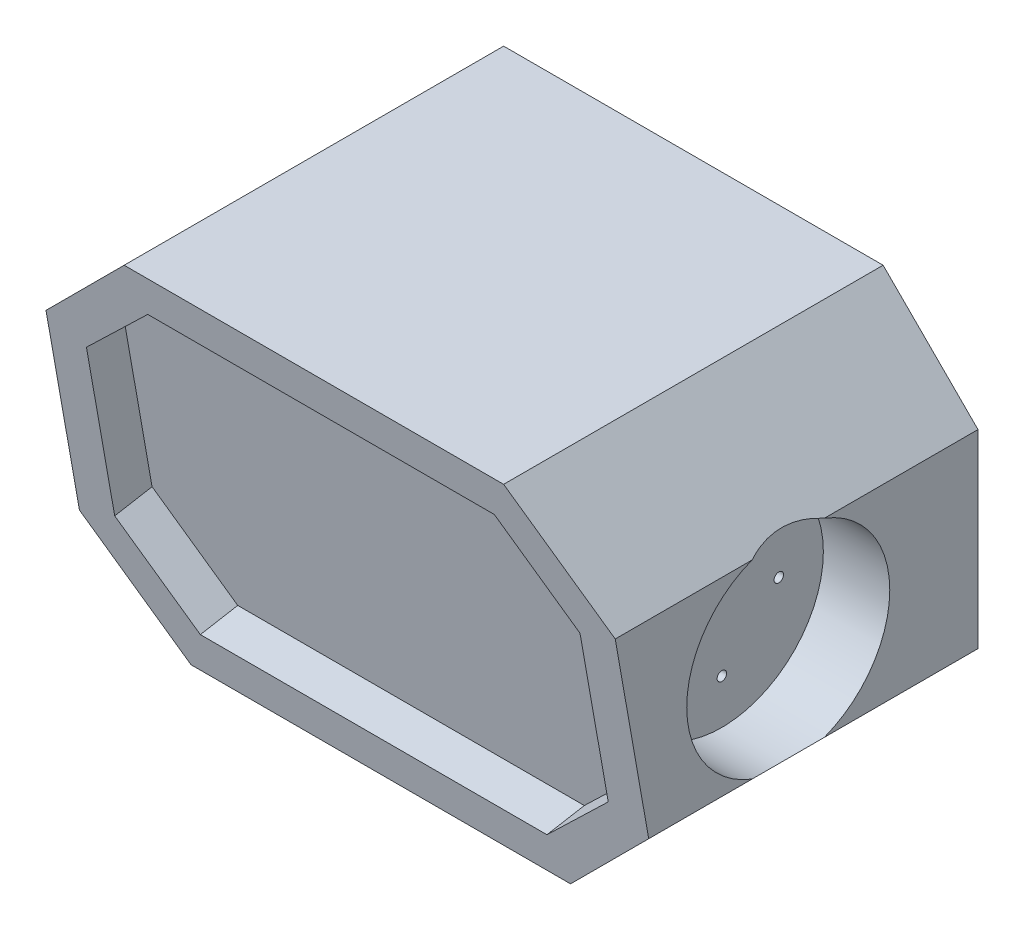
SolidWorks part; units mm, degrees
ref_plane "Front Plane" through (0, 0, 0) normal (0, 0, 1) x (1, 0, 0)
ref_plane "Top Plane" through (0, 0, 0) normal (0, 1, 0) x (1, 0, 0)
ref_plane "Right Plane" through (0, 0, 0) normal (1, 0, 0) x (0, 0, -1)
sketch "Sketch1" plane through (0, 0, 0) normal (1, 0, 0) x (0, 0, -1)
  line L1 (-100, -100) -> (100, -100)
  line L2 (-100, -100) -> (-100, 100)
  line L3 (-100, 100) -> (100, 100)
  line L4 (100, -100) -> (100, 100)
  line L5 (-100, -100) -> (100, 100) construction
  line L6 (-100, 100) -> (100, -100) construction
  point P0 (0, 0)
  dimension "D1" = 200
  dimension "D2" = 200
extrude "Boss-Extrude1" add sketch "Sketch1" against normal blind 150 contours L2 L1 L4 L3
sketch "Sketch2" plane through (0, 0, 0) normal (1, 0, 0) x (0, 0, -1)
  circle A0 centre (0, 0) radius 53.5
  dimension "D1" = 107
extrude "Cut-Extrude1" cut sketch "Sketch2" against normal blind 35
mirror "Mirror1" about plane through (-150, 0, 0) normal (1, 0, 0) of bodies 102 104
sketch "Sketch6" plane through (0, 0, 0) normal (1, 0, 0) x (0, 0, -1)
  line L0 (-100, 100) -> (-64.7346, -100)
  line L1 (-100, -100) -> (100, -100) construction
  line L2 (-64.7346, -100) -> (-100, -100)
  line L3 (-100, -100) -> (-100, 100)
  dimension "D1" = 80
extrude "Cut-Extrude3" cut sketch "Sketch6" against normal through all
chamfer "Chamfer2" distance 50 angle 45 4 edges at (0, 100, 0) (-300, 100, 0) (-300, -100, -17.6327) (0, -100, -17.6327)
sketch "Sketch8" plane through (0, -14.0856, 79.8836) normal (0, -0.1736, 0.9848) x (1, 0, 0)
  line L0 (-280, -28.2737) -> (-241.6259, -67.2397)
  line L1 (-241.6259, -67.2397) -> (-58.9661, -67.2397)
  line L2 (-58.9661, -67.2397) -> (-20, -28.8656)
  line L3 (-20, -28.8656) -> (-20, 56.8795)
  line L4 (-20, 56.8795) -> (-58.3741, 95.8456)
  line L5 (-58.3741, 95.8456) -> (-241.0339, 95.8456)
  line L6 (-241.0339, 95.8456) -> (-280, 57.4715)
  line L7 (-280, 57.4715) -> (-280, -28.2737)
  line L8 (-300, -36.4684) -> (-300, 65.0743) construction
  line L9 (0, -36.4684) -> (0, 65.0743) construction
  line L10 (0, 65.0743) -> (-50, 115.8456) construction
  line L13 (-250, 115.8456) -> (-50, 115.8456) construction
  line L14 (-250, -87.2397) -> (-50, -87.2397) construction
  line L15 (-300, -36.4684) -> (-250, -87.2397) construction
  dimension "D1" = 20
  dimension "D2" = 20
  dimension "D3" = 20
  dimension "D4" = 20
  dimension "D5" = 20
  dimension "D6" = 20
extrude "Cut-Extrude5" cut sketch "Sketch8" against normal blind 20
sketch "Sketch9" plane through (0, 0, -100) normal (0, 0, -1) x (-1, 0, 0)
  line L0 (250, -100) -> (50, -100) construction
  line L1 (150, 0) -> (150, 125) construction
  line L2 (150, 0) -> (61.6117, 88.3883) construction
  line L3 (150, 0) -> (238.3883, 88.3883) construction
  line L4 (150, 0) -> (61.6117, -88.3883) construction
  line L5 (150, 0) -> (238.3883, -88.3883) construction
  arc A0 (249.6157, -75.5097) -> (249.6157, 75.5097) centre (150, 0) ccw
  arc A1 (225.7079, -57.3874) -> (225.7079, 57.3874) centre (150, 0) ccw
  arc A2 (50.3843, 75.5097) -> (74.2921, 57.3874) centre (62.3382, 66.4486) cw
  arc A3 (225.7079, 57.3874) -> (249.6157, 75.5097) centre (237.6618, 66.4486) cw
  arc A4 (50.3843, -75.5097) -> (74.2921, -57.3874) centre (62.3382, -66.4486) ccw
  arc A5 (225.7079, -57.3874) -> (249.6157, -75.5097) centre (237.6618, -66.4486) ccw
  arc A6 (74.2921, 57.3874) -> (74.2921, -57.3874) centre (150, 0) ccw
  arc A7 (50.3843, 75.5097) -> (50.3843, -75.5097) centre (150, 0) ccw
  dimension "D3" = 190
  dimension "D4" = 250
  dimension "D1" = 100
  dimension "D2" = 150
  dimension "D5" = 45
  dimension "D6" = 45
  dimension "D7" = 90
extrude "Cut-Extrude6" cut sketch "Sketch9" against normal blind 20
sketch "Sketch10" plane through (0, 0, -100) normal (0, 0, -1) x (-1, 0, 0)
  line L0 (250, 100) -> (50, 100) construction
  arc A0 (74.2921, 57.3874) -> (74.2921, -57.3874) centre (150, 0) ccw
  arc A1 (50.3843, 75.5097) -> (50.3843, -75.5097) centre (150, 0) ccw
  arc A2 (74.2921, 57.3874) -> (50.3843, 75.5097) centre (62.3382, 66.4486) ccw
  arc A3 (249.6157, 75.5097) -> (225.7079, 57.3874) centre (237.6618, 66.4486) ccw
  arc A4 (225.7079, -57.3874) -> (249.6157, -75.5097) centre (237.6618, -66.4486) ccw
  arc A5 (50.3843, -75.5097) -> (74.2921, -57.3874) centre (62.3382, -66.4486) ccw
  arc A6 (225.7079, -57.3874) -> (225.7079, 57.3874) centre (150, 0) ccw
  arc A7 (249.6157, -75.5097) -> (249.6157, 75.5097) centre (150, 0) ccw
  arc A8 (70.3075, 60.4078) -> (70.3075, -60.4078) centre (150, 0) ccw
  arc A9 (54.369, 72.4894) -> (54.369, -72.4894) centre (150, 0) ccw
  arc A10 (245.631, 72.4894) -> (229.6925, 60.4078) centre (237.6618, 66.4486) ccw
  arc A11 (229.6925, -60.4078) -> (245.631, -72.4894) centre (237.6618, -66.4486) ccw
  arc A12 (54.369, -72.4894) -> (70.3075, -60.4078) centre (62.3382, -66.4486) ccw
  arc A13 (70.3075, 60.4078) -> (54.369, 72.4894) centre (62.3382, 66.4486) ccw
  arc A14 (245.631, -72.4894) -> (245.631, 72.4894) centre (150, 0) ccw
  arc A15 (229.6925, -60.4078) -> (229.6925, 60.4078) centre (150, 0) ccw
  dimension "D1" = 190
  dimension "D2" = 250
  dimension "D5" = 30
  dimension "D6" = 240
  dimension "D7" = 200
  dimension "D3" = 150
  dimension "D4" = 100
extrude "Boss-Extrude3" add sketch "Sketch10" against normal blind 9.2
sketch "Sketch11" plane through (0, 0, -100) normal (0, 0, -1) x (-1, 0, 0)
  line L0 (250, -100) -> (50, -100) construction
  line L1 (0, -50) -> (0, 50) construction
  circle A0 centre (150, 0) radius 53.5
  point P0 (150, 0)
  dimension "D3" = 107
  dimension "D1" = 100
  dimension "D2" = 150
extrude "Cut-Extrude7" cut sketch "Sketch11" against normal blind 35
sketch "Sketch12" plane through (-35, 0, 0) normal (1, 0, 0) x (0, 0, -1)
  circle A0 centre (0, 0) radius 30 construction
  circle A1 centre (0, 30) radius 2.5
  circle A2 centre (30, 0) radius 2.5
  circle A3 centre (0, -30) radius 2.5
  circle A4 centre (-30, 0) radius 2.5
  dimension "D1" = 60
  dimension "D2" = 5
  dimension "D3" = 5
  dimension "D4" = 5
  dimension "D5" = 5
extrude "Cut-Extrude8" cut sketch "Sketch12" against normal blind 10 contours A1 | A4 | A3 | A2
ref_plane "Plane1" through (-150, 0, 0) normal (1, 0, 0) x (0, 0, -1)
mirror "Mirror2" about plane through (-150, 0, 0) normal (1, 0, 0) of "Cut-Extrude8"
sketch "Sketch13" plane through (0, 0, -65) normal (0, 0, -1) x (-1, 0, 0)
  circle A0 centre (150, 0) radius 25 construction
  circle A1 centre (150, 0) radius 53.5
  circle A2 centre (150, 0) radius 53.5
  circle A3 centre (150, 25) radius 2.5
  circle A4 centre (150, -25) radius 2.5
  circle A5 centre (175, 0) radius 2.5
  circle A6 centre (125, 0) radius 2.5
  dimension "D2" = 50
  dimension "D3" = 5
  dimension "D4" = 5
  dimension "D5" = 5
  dimension "D6" = 5
  dimension "D1" = 0
extrude "Cut-Extrude9" cut sketch "Sketch13" against normal blind 10 contours A6 | A4 | A5 | A3
sketch "Sketch14" plane through (-150, 0, 0) normal (1, 0, 0) x (0, 0, -1)
  line L0 (-64.7346, -100) -> (100, -100) construction
  line L1 (55, 22.5) -> (55, 27.5) construction
  line L2 (100, 100) -> (-100, 100) construction
  line L3 (-76.8309, 83.7768) -> (-70.1673, 45.9857) construction
  line L4 (-64.7346, -100) -> (100, -100)
  line L5 (55, 22.5) -> (55, 27.5)
  line L6 (100, 100) -> (-100, 100)
  line L7 (-76.8309, 83.7768) -> (-70.1673, 45.9857)
  line L8 (-67.7739, 90) -> (-36.0351, -90)
  line L9 (-36.0351, -90) -> (55, -90)
  line L10 (55, -90) -> (55, 90)
  line L11 (55, 90) -> (-67.7739, 90)
  dimension "D1" = 10
  dimension "D2" = 0
  dimension "D3" = 10
  dimension "D4" = 10
extrude "Cut-Extrude10" cut sketch "Sketch14" against normal mid plane 210 contours L8 L9 L10 L11
sketch "Sketch15" plane through (0, -100, 0) normal (0, -1, 0) x (1, 0, 0)
  line L0 (-203.5, -65) -> (-96.5, -65) construction
  line L1 (-203.5, -65) -> (-96.5, -65)
  line L2 (-150, -65) -> (-150, -15) construction
  line L4 (-50, 64.7346) -> (-250, 64.7346)
  line L5 (-250, 64.7346) -> (-250, -100)
  line L6 (-250, -100) -> (-50, -100)
  line L7 (-50, -100) -> (-50, 64.7346)
  line L8 (-50, 64.7346) -> (-250, 64.7346)
  line L9 (-250, 64.7346) -> (-250, -100)
  line L10 (-250, -100) -> (-50, -100)
  line L11 (-50, -100) -> (-50, 64.7346)
  line L12 (-60, 25) -> (-240, 25)
  line L13 (-60, 25) -> (-60, -55)
  line L14 (-60, -55) -> (-240, -55)
  line L15 (-240, 25) -> (-240, -55)
  line L16 (-60, 25) -> (-240, -55) construction
  line L17 (-60, -55) -> (-240, 25) construction
  dimension "D2" = 80
  dimension "D3" = 180
  dimension "D4" = 10
  dimension "D1" = 0
extrude "Cut-Extrude11" cut sketch "Sketch15" against normal blind 10 contours L15 L14 L13 L12
sketch "Sketch17" plane through (0, -100, 0) normal (0, -1, 0) x (1, 0, 0)
  line L0 (-50, -100) -> (-50, 64.7346) construction
  line L1 (-250, 64.7346) -> (-250, -100) construction
  line L2 (-50, -100) -> (-50, 64.7346)
  line L3 (-250, 64.7346) -> (-250, -100)
  line L4 (-60, 25) -> (-240, 25)
  line L5 (-60, -55) -> (-60, 25)
  line L6 (-240, -55) -> (-60, -55)
  line L7 (-240, 25) -> (-240, -55)
  line L8 (-60, 25) -> (-240, 25)
  line L9 (-60, -55) -> (-60, 25)
  line L10 (-240, -55) -> (-60, -55)
  line L11 (-240, 25) -> (-240, -55)
  line L12 (-242.5, 25) -> (-242.5, -55) construction
  line L13 (-240, 25) -> (-245, 25)
  line L14 (-240, 25) -> (-240, -55)
  line L15 (-240, -55) -> (-245, -55)
  line L16 (-245, 25) -> (-245, -55)
  line L17 (-240, 25) -> (-245, -55) construction
  line L18 (-240, -55) -> (-245, 25) construction
  line L19 (-60, 25) -> (-55, 25)
  line L20 (-60, 25) -> (-60, -55)
  line L21 (-60, -55) -> (-55, -55)
  line L22 (-55, 25) -> (-55, -55)
  line L23 (-60, 25) -> (-55, -55) construction
  line L24 (-60, -55) -> (-55, 25) construction
  line L25 (-242.5, 15) -> (-242.5, -65) construction
  line L26 (-242.5, 5) -> (-242.5, -75) construction
  line L27 (-242.5, -5) -> (-242.5, -85) construction
  line L28 (-242.5, -15) -> (-242.5, -95) construction
  line L29 (-242.5, -25) -> (-242.5, -105) construction
  line L30 (-242.5, -35) -> (-242.5, -115) construction
  line L31 (-242.5, -45) -> (-242.5, -125) construction
  line L32 (-150, 25) -> (-150, -55) construction
  circle A0 centre (-242.5, 20) radius 1.5
  circle A1 centre (-242.5, 10) radius 1.5
  circle A2 centre (-242.5, 0) radius 1.5
  circle A3 centre (-242.5, -10) radius 1.5
  circle A4 centre (-242.5, -20) radius 1.5
  circle A5 centre (-242.5, -30) radius 1.5
  circle A6 centre (-242.5, -40) radius 1.5
  circle A7 centre (-242.5, -50) radius 1.5
  circle A8 centre (-57.5, 20) radius 1.5
  circle A9 centre (-57.5, 10) radius 1.5
  circle A10 centre (-57.5, 0) radius 1.5
  circle A11 centre (-57.5, -10) radius 1.5
  circle A12 centre (-57.5, -20) radius 1.5
  circle A13 centre (-57.5, -30) radius 1.5
  circle A14 centre (-57.5, -40) radius 1.5
  circle A15 centre (-57.5, -50) radius 1.5
  point P11 (-242.5, -15)
  point P15 (-57.5, -15)
  dimension "D4" = 3
  dimension "D2" = 5
  dimension "D3" = 5
  dimension "D5" = 5
  dimension "D7" = 5
  dimension "D1" = 0
  dimension "D6" = 8
extrude "Cut-Extrude12" cut sketch "Sketch17" against normal blind 5 contours L19 L22 L21 L20 | L13 L16 L15 L14
extrude "Cut-Extrude13" cut sketch "Sketch17<3>" against normal blind 10 contours A11 | A0 | A1 | A2 | A3 | A4 | A5 | A6 | A7 | A15 | A14 | A13 | A12 | A10 | A9 | A8 region at (-57.5, -100, -10)
sketch "Sketch17<3>" plane through (0, -100, 0) normal (0, -1, 0) x (1, 0, 0) same geometry as "Sketch17"
